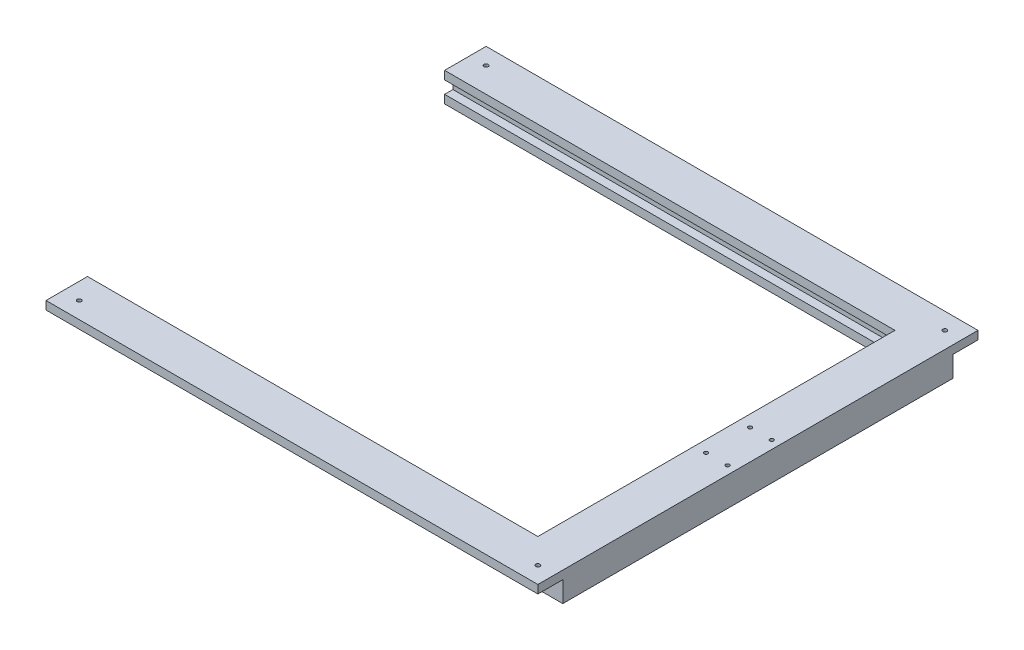
SolidWorks part; units mm, degrees
ref_plane "Спереди" through (0, 0, 0) normal (0, 0, 1) x (1, 0, 0)
ref_plane "Сверху" through (0, 0, 0) normal (0, 1, 0) x (1, 0, 0)
ref_plane "Справа" through (0, 0, 0) normal (1, 0, 0) x (0, 0, -1)
sketch "Эскиз1" plane through (0, 0, 0) normal (0, 1, 0) x (1, 0, 0)
  line L0 (50, -77.9215) -> (50, -607.9215)
  line L1 (-542.3, -77.9215) -> (50, -77.9215)
  line L2 (-542.3, -77.9215) -> (-542.3, -127.9215)
  line L3 (-542.3, -607.9215) -> (50, -607.9215)
  line L5 (-542.3, -127.9215) -> (0, -127.9215)
  line L7 (-542.3, -557.9215) -> (0, -557.9215)
  line L13 (-542.3, -557.9215) -> (-542.3, -607.9215)
  line L22 (0, -127.9215) -> (0, -557.9215)
  dimension "D1" = 592.3
  dimension "D12" = 50
  dimension "D2" = 530
  dimension "D3" = 50
  dimension "D4" = 50
  dimension "D9" = 50
  dimension "D8" = 77.9215
extrude "Бобышка-Вытянуть2" add sketch "Эскиз1" along normal blind 10
sketch "Эскиз2" plane through (0, 0, 0) normal (0, -1, 0) x (1, 0, 0)
  line L0 (-542.3, 127.9215) -> (0, 127.9215) construction
  line L5 (50, 607.9215) -> (50, 77.9215) construction
  line L6 (0, 557.9215) -> (-542.3, 557.9215) construction
  line L18 (50, 577.9215) -> (50, 107.9215)
  line L20 (10, 567.9215) -> (10, 117.9215)
  line L21 (-542.3, 77.9215) -> (-542.3, 127.9215) construction
  line L22 (50, 107.9215) -> (-542.3, 107.9215)
  line L24 (10, 117.9215) -> (-542.3, 117.9215)
  line L25 (-542.3, 107.9215) -> (-542.3, 117.9215)
  line L26 (-542.3, 557.9215) -> (-542.3, 607.9215) construction
  line L27 (50, 577.9215) -> (-542.3, 577.9215)
  line L29 (10, 567.9215) -> (-542.3, 567.9215)
  line L30 (-542.3, 577.9215) -> (-542.3, 567.9215)
  dimension "D1" = 40
  dimension "D2" = 10
  dimension "D3" = 10
  dimension "D4" = 10
  dimension "D5" = 10
extrude "Бобышка-Вытянуть3" add sketch "Эскиз2" along normal blind 15
sketch "Эскиз4" plane through (0, 10, 0) normal (0, 1, 0) x (1, 0, 0)
  line L0 (50, -77.9215) -> (-542.3, -77.9215) construction
  line L1 (-542.3, -77.9215) -> (-542.3, -127.9215) construction
  circle A0 centre (-522.3, -97.9215) radius 2.5
  dimension "D1" = 5
  dimension "D2" = 20
  dimension "D3" = 20
extrude "Вырез-Вытянуть1" cut sketch "Эскиз4" against normal through all
pattern_linear "Линейный массив2" count 2 spacing 552.3 along (1, 0, 0) count 2 spacing 490 along (0, 0, 1) of "Вырез-Вытянуть1"
sketch "Эскиз5" plane through (0, -15, 0) normal (0, -1, 0) x (1, 0, 0)
  line L8 (50, 577.9215) -> (-542.3, 577.9215)
  line L9 (-542.3, 577.9215) -> (-542.3, 557.9215)
  line L10 (-542.3, 557.9215) -> (0, 557.9215)
  line L11 (0, 557.9215) -> (0, 127.9215)
  line L12 (0, 127.9215) -> (-542.3, 127.9215)
  line L13 (-542.3, 127.9215) -> (-542.3, 107.9215)
  line L14 (-542.3, 107.9215) -> (50, 107.9215)
  line L15 (50, 107.9215) -> (50, 577.9215)
extrude "Бобышка-Вытянуть4" add sketch "Эскиз5" along normal blind 10
sketch "Эскиз6" plane through (0, -25, 0) normal (0, -1, 0) x (1, 0, 0)
  line L1 (40, 316.4215) -> (14, 316.4215) construction
  line L2 (40, 316.4215) -> (40, 369.4215) construction
  line L3 (40, 369.4215) -> (14, 369.4215) construction
  line L4 (14, 316.4215) -> (14, 369.4215) construction
  line L5 (50, 107.9215) -> (50, 577.9215) construction
  circle A1 centre (14, 369.4215) radius 2.25
  circle A2 centre (40, 369.4215) radius 2.25
  circle A3 centre (40, 316.4215) radius 2.25
  circle A4 centre (14, 316.4215) radius 2.25
  point P4 (50, 342.9215)
  point P6 (40, 342.9215)
  dimension "D4" = 4.5
  dimension "D1" = 53
  dimension "D2" = 26
  dimension "D3" = 10
extrude "Вырез-Вытянуть2" cut sketch "Эскиз6" against normal through all
equation "\"Ширина груза\"= 420"
equation "\"Глубина груза\"= 490"
equation "\"Высота груза\"= 297"
equation "\"Ширина ячейки\"= \"Ширина груза\" + 10"
equation "\"Глубина ячейки\"= \"Глубина груза\" + 10"
equation "\"Высота ячейки\"= \"Высота груза\" + 10 + 13"
equation "\"Колво ячеек ширина\"= 2"
equation "\"Колво ячеек высота\"= 2"
equation "\"Толщина стенки\"= 10"
equation "\"Крепление дверцы\"= 5"
equation "\"Ширина рейки\"= \"Толщина шестерни\""
equation "\"Высота рейки\"= 20"
equation "\"Высота пола\"= 20"
equation "\"Колво полозьев\"= 5"
equation "\"Отступ рейки\"= 20"
equation "\"Глубина каретки\"= \"Глубина ячейки\" + 30 + \"Мотор Y высота корпуса\" + 20"
equation "\"Длинна рейки\"= ( \"Ширина ячейки\" + \"Толщина стенки\" + \"Крепление дверцы\" ) * \"Колво ячеек ширина\" + \"Ширина ячейки выгрузки\" * \"Колво выгрузки\" + \"Толщина стенки\""
equation "\"Отступ шпильки\"= 20"
equation "\"Диаметр шпильки\"= 5"
equation "\"Длинна шпильки\"= ( \"Высота ячейки\" + \"Толщина стенки\" + \"Высота пола\" ) * \"Колво ячеек высота\" + ( \"Толщина стенки\" + \"Отступ рейки\" ) * 2 "
equation "\"D2@Эскиз1\"=\"Ширина ячейки\" + \"Ширина пластины\" * 2 "
equation "\"D9@Эскиз1\"=\"Ширина пластины\""
equation "\"D3@Эскиз1\"=\"Ширина пластины\""
equation "\"D4@Эскиз1\"= \"Ширина пластины\""
equation "\"Ширина пластины\"= 50  "
equation "\"D1@Бобышка-Вытянуть2\"=\"Толщина стенки\""
equation "\"D1@Эскиз4\"= \"Диаметр шпильки\""
equation "\"D4@Линейный массив2\"=\"Ширина ячейки\" + \"Ширина пластины\" * 2  - \"Отступ шпильки\" * 2"
equation "\"D1@Эскиз1\"= \"Глубина каретки\""
equation "\"D3@Линейный массив2\"= \"Глубина каретки\" - \"Отступ шпильки\" * 2"
equation "\"D2@Эскиз4\"=\"Отступ шпильки\""
equation "\"D3@Эскиз4\"= \"Отступ шпильки\""
equation "\"D1@Эскиз2\"= \"Ширина пластины\" - \"Толщина стенки\""
equation "\"D2@Эскиз2\"= \"Толщина стенки\""
equation "\"D3@Эскиз2\"= \"Толщина стенки\""
equation "\"D4@Эскиз2\"= \"Толщина стенки\""
equation "\"D5@Эскиз2\"= \"Толщина стенки\""
equation "\"D1@Бобышка-Вытянуть4\"= \"Толщина стенки\""
equation "\"Вы\"=20"
equation "\"D1@Бобышка-Вытянуть3\"=\"Высота пола\" - 5"
equation "\"Высота зона выгрузки\"= \"Высота ячейки\" * 2 + \"Толщина стенки\" * 2"
equation "\"Колво выгрузки\"= 1"
equation "\"Ширина ячейки выгрузки\"= \"Ширина ячейки\" + \"Толщина стенки\" + \"Отступ крепления мотора фиксации\"*2"
equation "\"Отступ крепления мотора фиксации\" = 30"
equation "\"Мотор X ширина корпуса\"= 42.3"
equation "\"Мотор X высота корпуса\"= 42.3"
equation "\"Мотор X длина корпуса\"= 40"
equation "\"Мотор X вылет вала\"= 19.8"
equation "\"Мотор Y ширина корпуса\"= 42.3"
equation "\"Мотор Y высота корпуса\"= 42.3"
equation "\"Мотор Y длина корпуса\"= 48"
equation "\"Мотор Y вылет вала\"= 30"
equation "\"Мотор Z ширина корпуса\"= 42"
equation "\"Мотор Z высота корпуса\"= 42"
equation "\"Мотор Z длина корпуса\"= 40"
equation "\"Мотор Z вылет вала\"= 23"
equation "\"Мотор диаметр вала ПРЕДВ\"= 5"
equation "\"Мотор шаг крепления ПРЕДВ\"= 31"
equation "\"Мотор диаметр отверстий ПРЕДВ\"= 3"
equation "\"Мотор глубина отверстий ПРЕДВ\"= 4.5"
equation "\"Мотор диаметр буртика ПРЕДВ\"= 22"
equation "\"Мотор высота буртика ПРЕДВ\"= 2"
equation "\"Мотор диаметр шкива ПРЕДВ\"= 16"
equation "\"Мотор длина шкива ПРЕДВ\"= 12"
equation "\"Мотор отступ шкива ПРЕДВ\"= 5"
equation "\"Мотор X шаг градусов\"= 1.8"
equation "\"Мотор X ток А\"= 1.5"
equation "\"Мотор X сопротивление Ом\"= 1.3"
equation "\"Мотор X индуктивность мГн\"= 2"
equation "\"Мотор Y шаг градусов\"= 1.8"
equation "\"Мотор Y ток А\"= 2.2"
equation "\"Мотор Y сопротивление Ом\"= 0.9"
equation "\"Мотор Y индуктивность мГн\"= 2"
equation "\"Мотор Z шаг градусов\"= 1.8"
equation "\"Мотор Z ток А\"= 1"
equation "\"Мотор Z сопротивление Ом\"= 4"
equation "\"Мотор Z индуктивность мГн\"= 8"
equation "\"Мотор Y диаметр ротора\"= 25.78"
